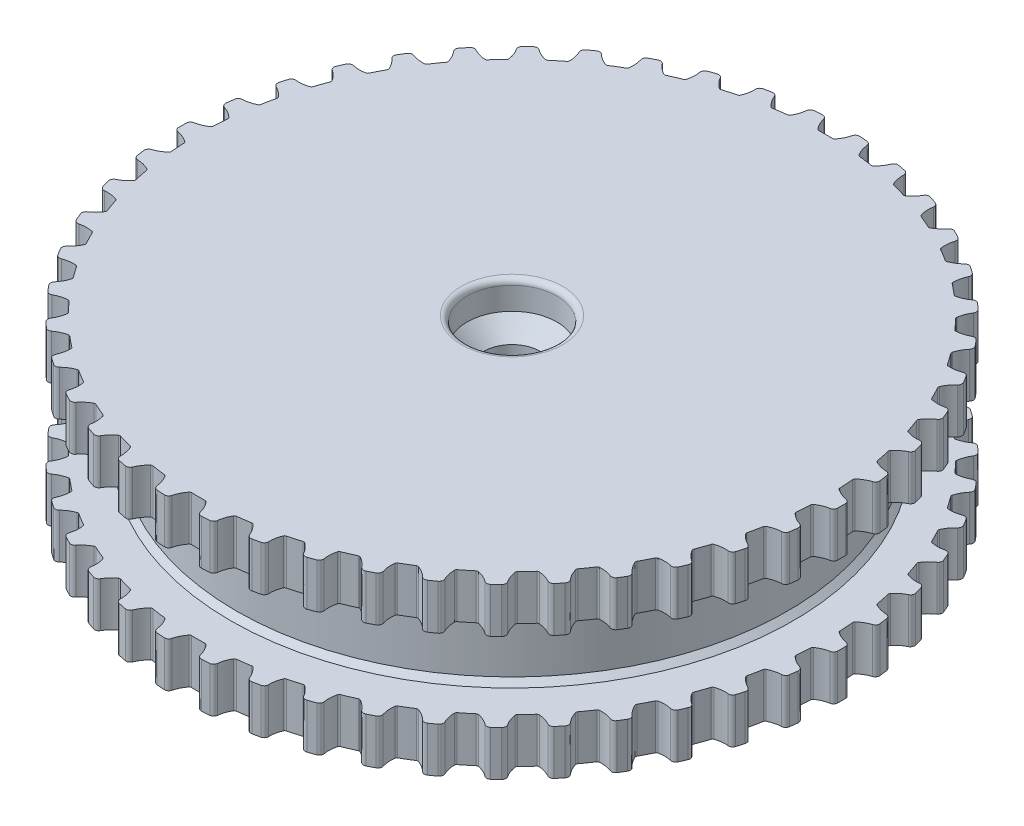
SolidWorks part; units mm, degrees
ref_plane "Front Plane" through (0, 0, 0) normal (0, 0, 1) x (1, 0, 0)
ref_plane "Top Plane" through (0, 0, 0) normal (0, 1, 0) x (1, 0, 0)
ref_plane "Right Plane" through (0, 0, 0) normal (1, 0, 0) x (0, 0, -1)
sketch "Sketch1" plane through (0, 0, 0) normal (0, 1, 0) x (1, 0, 0)
  circle A0 centre (0, 0) radius 62.5
  dimension "D1" = 125
extrude "Boss-Extrude1" add sketch "Sketch1" along normal blind 2
sketch "Sketch2" plane through (0, 2, 0) normal (0, 1, 0) x (1, 0, 0)
  line L0 (0, 0) -> (0, 59.255) construction
  line L2 (2.6, 59.1979) -> (2.6, 58.5113) construction
  line L3 (2.6, 58.5113) -> (-2.6, 58.5113) construction
  line L4 (-2.6, 58.5113) -> (-2.6, 59.1979) construction
  line L5 (0, 0) -> (8.0686, 58.7031) construction
  line L6 (0, 58.569) -> (7.9751, 58.0235) construction
  circle A0 centre (0, 0) radius 59.255 construction
  arc A1 (-54.2415, -22.0951) -> (-53.1706, -24.5605) centre (0, 0) ccw construction
  arc A2 (-2.655, 58.5088) -> (-1.5289, 55.875) centre (2.6, 59.1979) ccw
  circle A4 centre (0, 0) radius 55.739 construction
  arc A6 (1.5289, 55.875) -> (2.655, 58.5088) centre (-2.6, 59.1979) ccw
  arc A7 (1.2087, 55.7259) -> (-1.2087, 55.7259) centre (0, 0) ccw
  arc A8 (-1.5289, 55.875) -> (-1.2087, 55.7259) centre (-1.2173, 56.1258) ccw
  arc A9 (1.2087, 55.7259) -> (1.5289, 55.875) centre (1.2173, 56.1258) ccw
  arc A10 (8.7854, 55.0423) -> (6.3906, 55.3715) centre (0, 0) ccw
  arc A11 (8.7854, 55.0423) -> (9.123, 55.1464) centre (8.8485, 55.4373) ccw
  arc A12 (9.123, 55.1464) -> (10.5972, 57.6023) centre (5.485, 59.0006) ccw
  arc A13 (5.3367, 58.3254) -> (6.0936, 55.5628) centre (10.6366, 58.2925) ccw
  arc A14 (6.0936, 55.5628) -> (6.3906, 55.3715) centre (6.4365, 55.7688) ccw
  arc A15 (16.1985, 53.3334) -> (13.8708, 53.9855) centre (0, 0) ccw
  arc A16 (16.1985, 53.3334) -> (16.5472, 53.3905) centre (16.3148, 53.7161) ccw
  arc A17 (16.5472, 53.3905) -> (18.342, 55.6228) centre (13.4678, 57.7042) ccw
  arc A18 (13.2289, 57.0555) -> (13.6027, 54.2155) centre (18.475, 56.3013) ccw
  arc A19 (13.6027, 54.2155) -> (13.8708, 53.9855) centre (13.9704, 54.373) ccw
  arc A20 (23.3099, 50.6309) -> (21.0927, 51.594) centre (0, 0) ccw
  arc A21 (23.3099, 50.6309) -> (23.663, 50.6401) centre (23.4771, 50.9942) ccw
  arc A22 (23.663, 50.6401) -> (25.7452, 52.6072) centre (21.1998, 55.3329) ccw
  arc A23 (20.8748, 54.7227) -> (20.8583, 51.8583) centre (25.9693, 53.2612) ccw
  arc A24 (20.8583, 51.8583) -> (21.0927, 51.594) centre (21.244, 51.9642) ccw
  arc A25 (29.987, 46.9853) -> (27.9216, 48.2413) centre (0, 0) ccw
  arc A26 (29.987, 46.9853) -> (30.3381, 46.9463) centre (30.2022, 47.3225) ccw
  arc A27 (30.3381, 46.9463) -> (32.6687, 48.6116) centre (28.5368, 51.9308) ccw
  arc A28 (28.1318, 51.3706) -> (27.7254, 48.5351) centre (32.9798, 49.229) ccw
  arc A29 (27.7254, 48.5351) -> (27.9216, 48.2413) centre (28.122, 48.5875) ccw
  arc A30 (36.1055, 42.4645) -> (34.2304, 43.99) centre (0, 0) ccw
  arc A31 (36.1055, 42.4645) -> (36.4481, 42.378) centre (36.3646, 42.7692) ccw
  arc A32 (36.4481, 42.378) -> (38.9837, 43.7104) centre (35.3423, 47.5613) ccw
  arc A33 (34.8647, 47.0615) -> (34.076, 44.3078) centre (39.376, 44.2797) ccw
  arc A34 (34.076, 44.3078) -> (34.2304, 43.99) centre (34.476, 44.3057) ccw
  arc A35 (41.5515, 37.1526) -> (39.9015, 38.9192) centre (0, 0) ccw
  arc A36 (41.5515, 37.1526) -> (41.8791, 37.0203) centre (41.8497, 37.4192) ccw
  arc A37 (41.8791, 37.0203) -> (44.5725, 37.995) centre (41.4894, 42.3059) ccw
  arc A38 (40.9482, 41.8757) -> (39.7919, 39.2551) centre (45.0386, 38.5056) ccw
  arc A39 (39.7919, 39.2551) -> (39.9015, 38.9192) centre (40.1879, 39.1985) ccw
  arc A40 (46.2234, 31.1486) -> (44.8294, 33.1235) centre (0, 0) ccw
  arc A41 (46.2234, 31.1486) -> (46.5299, 30.9729) centre (46.5551, 31.3721) ccw
  arc A42 (46.5299, 30.9729) -> (49.331, 31.5718) centre (46.8636, 36.2624) ccw
  arc A43 (46.2688, 35.9099) -> (44.7665, 33.4711) centre (49.8623, 32.0142) ccw
  arc A44 (44.7665, 33.4711) -> (44.8294, 33.1235) centre (45.1511, 33.3612) ccw
  arc A45 (50.0343, 24.5644) -> (48.9222, 26.7107) centre (0, 0) ccw
  arc A46 (50.0343, 24.5644) -> (50.314, 24.3486) centre (50.3933, 24.7407) ccw
  arc A47 (50.314, 24.3486) -> (53.1706, 24.5605) centre (51.3648, 29.5434) ccw
  arc A48 (50.7276, 29.2752) -> (48.9072, 27.0637) centre (53.7572, 24.9264) ccw
  arc A49 (48.9072, 27.0637) -> (48.9222, 26.7107) centre (49.2732, 26.9024) ccw
  arc A50 (52.9131, 17.5226) -> (52.1036, 19.8003) centre (0, 0) ccw
  arc A51 (52.9131, 17.5226) -> (53.1609, 17.2707) centre (53.2928, 17.6483) ccw
  arc A52 (53.1609, 17.2707) -> (56.0197, 17.0917) centre (54.9092, 22.2741) ccw
  arc A53 (54.2415, 22.0951) -> (52.1368, 20.1521) centre (56.6506, 17.3743) ccw
  arc A54 (52.1368, 20.1521) -> (52.1036, 19.8003) centre (52.4775, 19.9424) ccw
  arc A55 (54.8063, 10.1544) -> (54.3144, 12.5211) centre (0, 0) ccw
  arc A56 (54.8063, 10.1544) -> (55.0174, 9.8711) centre (55.1996, 10.2273) ccw
  arc A57 (55.0174, 9.8711) -> (57.8252, 9.3045) centre (57.4308, 14.5898) ccw
  arc A58 (56.7449, 14.5034) -> (54.3953, 12.8651) centre (58.4888, 9.4986) ccw
  arc A59 (54.3953, 12.8651) -> (54.3144, 12.5211) centre (54.7042, 12.611) ccw
  arc A60 (55.6785, 2.597) -> (55.5135, 5.0087) centre (0, 0) ccw
  arc A61 (55.6785, 2.597) -> (55.8491, 2.2877) centre (56.0781, 2.6157) ccw
  arc A62 (55.8491, 2.2877) -> (58.5536, 1.344) centre (58.8825, 6.6337) ccw
  arc A63 (58.1912, 6.6416) -> (55.6404, 5.3384) centre (59.2374, 1.4459) ccw
  arc A64 (55.6404, 5.3384) -> (55.5135, 5.0087) centre (55.9119, 5.0447) ccw
  arc A65 (55.5135, -5.0087) -> (55.6785, -2.597) centre (0, 0) ccw
  arc A66 (55.5135, -5.0087) -> (55.6404, -5.3384) centre (55.9119, -5.0447) ccw
  arc A67 (55.6404, -5.3384) -> (58.1912, -6.6416) centre (59.2374, -1.4459) ccw
  arc A68 (58.5536, -1.344) -> (55.8491, -2.2877) centre (58.8825, -6.6337) ccw
  arc A69 (55.8491, -2.2877) -> (55.6785, -2.597) centre (56.0781, -2.6157) ccw
  arc A70 (54.3144, -12.5211) -> (54.8063, -10.1544) centre (0, 0) ccw
  arc A71 (54.3144, -12.5211) -> (54.3953, -12.8651) centre (54.7042, -12.611) ccw
  arc A72 (54.3953, -12.8651) -> (56.7449, -14.5034) centre (58.4888, -9.4986) ccw
  arc A73 (57.8252, -9.3045) -> (55.0174, -9.8711) centre (57.4308, -14.5898) ccw
  arc A74 (55.0174, -9.8711) -> (54.8063, -10.1544) centre (55.1996, -10.2273) ccw
  arc A75 (52.1036, -19.8003) -> (52.9131, -17.5226) centre (0, 0) ccw
  arc A76 (52.1036, -19.8003) -> (52.1368, -20.1521) centre (52.4775, -19.9424) ccw
  arc A77 (52.1368, -20.1521) -> (54.2415, -22.0951) centre (56.6506, -17.3743) ccw
  arc A78 (56.0197, -17.0917) -> (53.1609, -17.2707) centre (54.9092, -22.2741) ccw
  arc A79 (53.1609, -17.2707) -> (52.9131, -17.5226) centre (53.2928, -17.6483) ccw
  arc A80 (48.9222, -26.7107) -> (50.0343, -24.5644) centre (0, 0) ccw
  arc A81 (48.9222, -26.7107) -> (48.9072, -27.0637) centre (49.2732, -26.9024) ccw
  arc A82 (48.9072, -27.0637) -> (50.7276, -29.2752) centre (53.7572, -24.9264) ccw
  arc A83 (53.1706, -24.5605) -> (50.314, -24.3486) centre (51.3648, -29.5434) ccw
  arc A84 (50.314, -24.3486) -> (50.0343, -24.5644) centre (50.3933, -24.7407) ccw
  arc A85 (44.8294, -33.1235) -> (46.2234, -31.1486) centre (0, 0) ccw
  arc A86 (44.8294, -33.1235) -> (44.7665, -33.4711) centre (45.1511, -33.3612) ccw
  arc A87 (44.7665, -33.4711) -> (46.2688, -35.9099) centre (49.8623, -32.0142) ccw
  arc A88 (49.331, -31.5718) -> (46.5299, -30.9729) centre (46.8636, -36.2624) ccw
  arc A89 (46.5299, -30.9729) -> (46.2234, -31.1486) centre (46.5551, -31.3721) ccw
  arc A90 (39.9015, -38.9192) -> (41.5515, -37.1526) centre (0, 0) ccw
  arc A91 (39.9015, -38.9192) -> (39.7919, -39.2551) centre (40.1879, -39.1985) ccw
  arc A92 (39.7919, -39.2551) -> (40.9482, -41.8757) centre (45.0386, -38.5056) ccw
  arc A93 (44.5725, -37.995) -> (41.8791, -37.0203) centre (41.4894, -42.3059) ccw
  arc A94 (41.8791, -37.0203) -> (41.5515, -37.1526) centre (41.8497, -37.4192) ccw
  arc A95 (34.2304, -43.99) -> (36.1055, -42.4645) centre (0, 0) ccw
  arc A96 (34.2304, -43.99) -> (34.076, -44.3078) centre (34.476, -44.3057) ccw
  arc A97 (34.076, -44.3078) -> (34.8647, -47.0615) centre (39.376, -44.2797) ccw
  arc A98 (38.9837, -43.7104) -> (36.4481, -42.378) centre (35.3423, -47.5613) ccw
  arc A99 (36.4481, -42.378) -> (36.1055, -42.4645) centre (36.3646, -42.7692) ccw
  arc A100 (27.9216, -48.2413) -> (29.987, -46.9853) centre (0, 0) ccw
  arc A101 (27.9216, -48.2413) -> (27.7254, -48.5351) centre (28.122, -48.5875) ccw
  arc A102 (27.7254, -48.5351) -> (28.1318, -51.3706) centre (32.9798, -49.229) ccw
  arc A103 (32.6687, -48.6116) -> (30.3381, -46.9463) centre (28.5368, -51.9308) ccw
  arc A104 (30.3381, -46.9463) -> (29.987, -46.9853) centre (30.2022, -47.3225) ccw
  arc A105 (21.0927, -51.594) -> (23.3099, -50.6309) centre (0, 0) ccw
  arc A106 (21.0927, -51.594) -> (20.8583, -51.8583) centre (21.244, -51.9642) ccw
  arc A107 (20.8583, -51.8583) -> (20.8748, -54.7227) centre (25.9693, -53.2612) ccw
  arc A108 (25.7452, -52.6072) -> (23.663, -50.6401) centre (21.1998, -55.3329) ccw
  arc A109 (23.663, -50.6401) -> (23.3099, -50.6309) centre (23.4771, -50.9942) ccw
  arc A110 (13.8708, -53.9855) -> (16.1985, -53.3334) centre (0, 0) ccw
  arc A111 (13.8708, -53.9855) -> (13.6027, -54.2155) centre (13.9704, -54.373) ccw
  arc A112 (13.6027, -54.2155) -> (13.2289, -57.0555) centre (18.475, -56.3013) ccw
  arc A113 (18.342, -55.6228) -> (16.5472, -53.3905) centre (13.4678, -57.7042) ccw
  arc A114 (16.5472, -53.3905) -> (16.1985, -53.3334) centre (16.3148, -53.7161) ccw
  arc A115 (6.3906, -55.3715) -> (8.7854, -55.0423) centre (0, 0) ccw
  arc A116 (6.3906, -55.3715) -> (6.0936, -55.5628) centre (6.4365, -55.7688) ccw
  arc A117 (6.0936, -55.5628) -> (5.3367, -58.3254) centre (10.6366, -58.2925) ccw
  arc A118 (10.5972, -57.6023) -> (9.123, -55.1464) centre (5.485, -59.0006) ccw
  arc A119 (9.123, -55.1464) -> (8.7854, -55.0423) centre (8.8485, -55.4373) ccw
  arc A120 (-1.2087, -55.7259) -> (1.2087, -55.7259) centre (0, 0) ccw
  arc A121 (-1.2087, -55.7259) -> (-1.5289, -55.875) centre (-1.2173, -56.1258) ccw
  arc A122 (-1.5289, -55.875) -> (-2.655, -58.5088) centre (2.6, -59.1979) ccw
  arc A123 (2.655, -58.5088) -> (1.5289, -55.875) centre (-2.6, -59.1979) ccw
  arc A124 (1.5289, -55.875) -> (1.2087, -55.7259) centre (1.2173, -56.1258) ccw
  arc A125 (-8.7854, -55.0423) -> (-6.3906, -55.3715) centre (0, 0) ccw
  arc A126 (-8.7854, -55.0423) -> (-9.123, -55.1464) centre (-8.8485, -55.4373) ccw
  arc A127 (-9.123, -55.1464) -> (-10.5972, -57.6023) centre (-5.485, -59.0006) ccw
  arc A128 (-5.3367, -58.3254) -> (-6.0936, -55.5628) centre (-10.6366, -58.2925) ccw
  arc A129 (-6.0936, -55.5628) -> (-6.3906, -55.3715) centre (-6.4365, -55.7688) ccw
  arc A130 (-16.1985, -53.3334) -> (-13.8708, -53.9855) centre (0, 0) ccw
  arc A131 (-16.1985, -53.3334) -> (-16.5472, -53.3905) centre (-16.3148, -53.7161) ccw
  arc A132 (-16.5472, -53.3905) -> (-18.342, -55.6228) centre (-13.4678, -57.7042) ccw
  arc A133 (-13.2289, -57.0555) -> (-13.6027, -54.2155) centre (-18.475, -56.3013) ccw
  arc A134 (-13.6027, -54.2155) -> (-13.8708, -53.9855) centre (-13.9704, -54.373) ccw
  arc A135 (-23.3099, -50.6309) -> (-21.0927, -51.594) centre (0, 0) ccw
  arc A136 (-23.3099, -50.6309) -> (-23.663, -50.6401) centre (-23.4771, -50.9942) ccw
  arc A137 (-23.663, -50.6401) -> (-25.7452, -52.6072) centre (-21.1998, -55.3329) ccw
  arc A138 (-20.8748, -54.7227) -> (-20.8583, -51.8583) centre (-25.9693, -53.2612) ccw
  arc A139 (-20.8583, -51.8583) -> (-21.0927, -51.594) centre (-21.244, -51.9642) ccw
  arc A140 (-29.987, -46.9853) -> (-27.9216, -48.2413) centre (0, 0) ccw
  arc A141 (-29.987, -46.9853) -> (-30.3381, -46.9463) centre (-30.2022, -47.3225) ccw
  arc A142 (-30.3381, -46.9463) -> (-32.6687, -48.6116) centre (-28.5368, -51.9308) ccw
  arc A143 (-28.1318, -51.3706) -> (-27.7254, -48.5351) centre (-32.9798, -49.229) ccw
  arc A144 (-27.7254, -48.5351) -> (-27.9216, -48.2413) centre (-28.122, -48.5875) ccw
  arc A145 (-36.1055, -42.4645) -> (-34.2304, -43.99) centre (0, 0) ccw
  arc A146 (-36.1055, -42.4645) -> (-36.4481, -42.378) centre (-36.3646, -42.7692) ccw
  arc A147 (-36.4481, -42.378) -> (-38.9837, -43.7104) centre (-35.3423, -47.5613) ccw
  arc A148 (-34.8647, -47.0615) -> (-34.076, -44.3078) centre (-39.376, -44.2797) ccw
  arc A149 (-34.076, -44.3078) -> (-34.2304, -43.99) centre (-34.476, -44.3057) ccw
  arc A150 (-41.5515, -37.1526) -> (-39.9015, -38.9192) centre (0, 0) ccw
  arc A151 (-41.5515, -37.1526) -> (-41.8791, -37.0203) centre (-41.8497, -37.4192) ccw
  arc A152 (-41.8791, -37.0203) -> (-44.5725, -37.995) centre (-41.4894, -42.3059) ccw
  arc A153 (-40.9482, -41.8757) -> (-39.7919, -39.2551) centre (-45.0386, -38.5056) ccw
  arc A154 (-39.7919, -39.2551) -> (-39.9015, -38.9192) centre (-40.1879, -39.1985) ccw
  arc A155 (-46.2234, -31.1486) -> (-44.8294, -33.1235) centre (0, 0) ccw
  arc A156 (-46.2234, -31.1486) -> (-46.5299, -30.9729) centre (-46.5551, -31.3721) ccw
  arc A157 (-46.5299, -30.9729) -> (-49.331, -31.5718) centre (-46.8636, -36.2624) ccw
  arc A158 (-46.2688, -35.9099) -> (-44.7665, -33.4711) centre (-49.8623, -32.0142) ccw
  arc A159 (-44.7665, -33.4711) -> (-44.8294, -33.1235) centre (-45.1511, -33.3612) ccw
  arc A160 (-50.0343, -24.5644) -> (-48.9222, -26.7107) centre (0, 0) ccw
  arc A161 (-50.0343, -24.5644) -> (-50.314, -24.3486) centre (-50.3933, -24.7407) ccw
  arc A162 (-50.314, -24.3486) -> (-53.1706, -24.5605) centre (-51.3648, -29.5434) ccw
  arc A163 (-50.7276, -29.2752) -> (-48.9072, -27.0637) centre (-53.7572, -24.9264) ccw
  arc A164 (-48.9072, -27.0637) -> (-48.9222, -26.7107) centre (-49.2732, -26.9024) ccw
  arc A165 (-52.9131, -17.5226) -> (-52.1036, -19.8003) centre (0, 0) ccw
  arc A166 (-52.9131, -17.5226) -> (-53.1609, -17.2707) centre (-53.2928, -17.6483) ccw
  arc A167 (-53.1609, -17.2707) -> (-56.0197, -17.0917) centre (-54.9092, -22.2741) ccw
  arc A168 (-54.2415, -22.0951) -> (-52.1368, -20.1521) centre (-56.6506, -17.3743) ccw
  arc A169 (-52.1368, -20.1521) -> (-52.1036, -19.8003) centre (-52.4775, -19.9424) ccw
  arc A170 (-54.8063, -10.1544) -> (-54.3144, -12.5211) centre (0, 0) ccw
  arc A171 (-54.8063, -10.1544) -> (-55.0174, -9.8711) centre (-55.1996, -10.2273) ccw
  arc A172 (-55.0174, -9.8711) -> (-57.8252, -9.3045) centre (-57.4308, -14.5898) ccw
  arc A173 (-56.7449, -14.5034) -> (-54.3953, -12.8651) centre (-58.4888, -9.4986) ccw
  arc A174 (-54.3953, -12.8651) -> (-54.3144, -12.5211) centre (-54.7042, -12.611) ccw
  arc A176 (7.9751, 58.0235) -> (0, 58.569) centre (0, 0) ccw construction
  arc A177 (-2.655, 58.5088) -> (56.0197, 17.0917) centre (0, 0) ccw construction
  arc A179 (-6.3906, 55.3715) -> (-8.7854, 55.0423) centre (0, 0) ccw
  arc A180 (-6.3906, 55.3715) -> (-6.0936, 55.5628) centre (-6.4365, 55.7688) ccw
  arc A181 (-6.0936, 55.5628) -> (-5.3367, 58.3254) centre (-10.6366, 58.2925) ccw
  arc A182 (-10.5972, 57.6023) -> (-9.123, 55.1464) centre (-5.485, 59.0006) ccw
  arc A183 (-9.123, 55.1464) -> (-8.7854, 55.0423) centre (-8.8485, 55.4373) ccw
  circle A184 centre (0, 0) radius 58.569
  arc A212 (-55.6785, -2.597) -> (-55.5135, -5.0087) centre (0, 0) ccw
  arc A213 (-55.6785, -2.597) -> (-55.8491, -2.2877) centre (-56.0781, -2.6157) ccw
  arc A214 (-55.8491, -2.2877) -> (-58.5536, -1.344) centre (-58.8825, -6.6337) ccw
  arc A215 (-58.1912, -6.6416) -> (-55.6404, -5.3384) centre (-59.2374, -1.4459) ccw
  arc A216 (-55.6404, -5.3384) -> (-55.5135, -5.0087) centre (-55.9119, -5.0447) ccw
  arc A217 (-55.5135, 5.0087) -> (-55.6785, 2.597) centre (0, 0) ccw
  arc A218 (-55.5135, 5.0087) -> (-55.6404, 5.3384) centre (-55.9119, 5.0447) ccw
  arc A219 (-55.6404, 5.3384) -> (-58.1912, 6.6416) centre (-59.2374, 1.4459) ccw
  arc A220 (-58.5536, 1.344) -> (-55.8491, 2.2877) centre (-58.8825, 6.6337) ccw
  arc A221 (-55.8491, 2.2877) -> (-55.6785, 2.597) centre (-56.0781, 2.6157) ccw
  arc A222 (-54.3144, 12.5211) -> (-54.8063, 10.1544) centre (0, 0) ccw
  arc A223 (-54.3144, 12.5211) -> (-54.3953, 12.8651) centre (-54.7042, 12.611) ccw
  arc A224 (-54.3953, 12.8651) -> (-56.7449, 14.5034) centre (-58.4888, 9.4986) ccw
  arc A225 (-57.8252, 9.3045) -> (-55.0174, 9.8711) centre (-57.4308, 14.5898) ccw
  arc A226 (-55.0174, 9.8711) -> (-54.8063, 10.1544) centre (-55.1996, 10.2273) ccw
  arc A227 (-52.1036, 19.8003) -> (-52.9131, 17.5226) centre (0, 0) ccw
  arc A228 (-52.1036, 19.8003) -> (-52.1368, 20.1521) centre (-52.4775, 19.9424) ccw
  arc A229 (-52.1368, 20.1521) -> (-54.2415, 22.0951) centre (-56.6506, 17.3743) ccw
  arc A230 (-56.0197, 17.0917) -> (-53.1609, 17.2707) centre (-54.9092, 22.2741) ccw
  arc A231 (-53.1609, 17.2707) -> (-52.9131, 17.5226) centre (-53.2928, 17.6483) ccw
  arc A232 (-48.9222, 26.7107) -> (-50.0343, 24.5644) centre (0, 0) ccw
  arc A233 (-48.9222, 26.7107) -> (-48.9072, 27.0637) centre (-49.2732, 26.9024) ccw
  arc A234 (-48.9072, 27.0637) -> (-50.7276, 29.2752) centre (-53.7572, 24.9264) ccw
  arc A235 (-53.1706, 24.5605) -> (-50.314, 24.3486) centre (-51.3648, 29.5434) ccw
  arc A236 (-50.314, 24.3486) -> (-50.0343, 24.5644) centre (-50.3933, 24.7407) ccw
  arc A237 (-44.8294, 33.1235) -> (-46.2234, 31.1486) centre (0, 0) ccw
  arc A238 (-44.8294, 33.1235) -> (-44.7665, 33.4711) centre (-45.1511, 33.3612) ccw
  arc A239 (-44.7665, 33.4711) -> (-46.2688, 35.9099) centre (-49.8623, 32.0142) ccw
  arc A240 (-49.331, 31.5718) -> (-46.5299, 30.9729) centre (-46.8636, 36.2624) ccw
  arc A241 (-46.5299, 30.9729) -> (-46.2234, 31.1486) centre (-46.5551, 31.3721) ccw
  arc A242 (-39.9015, 38.9192) -> (-41.5515, 37.1526) centre (0, 0) ccw
  arc A243 (-39.9015, 38.9192) -> (-39.7919, 39.2551) centre (-40.1879, 39.1985) ccw
  arc A244 (-39.7919, 39.2551) -> (-40.9482, 41.8757) centre (-45.0386, 38.5056) ccw
  arc A245 (-44.5725, 37.995) -> (-41.8791, 37.0203) centre (-41.4894, 42.3059) ccw
  arc A246 (-41.8791, 37.0203) -> (-41.5515, 37.1526) centre (-41.8497, 37.4192) ccw
  arc A247 (-34.2304, 43.99) -> (-36.1055, 42.4645) centre (0, 0) ccw
  arc A248 (-34.2304, 43.99) -> (-34.076, 44.3078) centre (-34.476, 44.3057) ccw
  arc A249 (-34.076, 44.3078) -> (-34.8647, 47.0615) centre (-39.376, 44.2797) ccw
  arc A250 (-38.9837, 43.7104) -> (-36.4481, 42.378) centre (-35.3423, 47.5613) ccw
  arc A251 (-36.4481, 42.378) -> (-36.1055, 42.4645) centre (-36.3646, 42.7692) ccw
  arc A252 (-27.9216, 48.2413) -> (-29.987, 46.9853) centre (0, 0) ccw
  arc A253 (-27.9216, 48.2413) -> (-27.7254, 48.5351) centre (-28.122, 48.5875) ccw
  arc A254 (-27.7254, 48.5351) -> (-28.1318, 51.3706) centre (-32.9798, 49.229) ccw
  arc A255 (-32.6687, 48.6116) -> (-30.3381, 46.9463) centre (-28.5368, 51.9308) ccw
  arc A256 (-30.3381, 46.9463) -> (-29.987, 46.9853) centre (-30.2022, 47.3225) ccw
  arc A257 (-21.0927, 51.594) -> (-23.3099, 50.6309) centre (0, 0) ccw
  arc A258 (-21.0927, 51.594) -> (-20.8583, 51.8583) centre (-21.244, 51.9642) ccw
  arc A259 (-20.8583, 51.8583) -> (-20.8748, 54.7227) centre (-25.9693, 53.2612) ccw
  arc A260 (-25.7452, 52.6072) -> (-23.663, 50.6401) centre (-21.1998, 55.3329) ccw
  arc A261 (-23.663, 50.6401) -> (-23.3099, 50.6309) centre (-23.4771, 50.9942) ccw
  arc A262 (-13.8708, 53.9855) -> (-16.1985, 53.3334) centre (0, 0) ccw
  arc A263 (-13.8708, 53.9855) -> (-13.6027, 54.2155) centre (-13.9704, 54.373) ccw
  arc A264 (-13.6027, 54.2155) -> (-13.2289, 57.0555) centre (-18.475, 56.3013) ccw
  arc A265 (-18.342, 55.6228) -> (-16.5472, 53.3905) centre (-13.4678, 57.7042) ccw
  arc A266 (-16.5472, 53.3905) -> (-16.1985, 53.3334) centre (-16.3148, 53.7161) ccw
  arc A277 (-50.7276, -29.2752) -> (-56.0197, -17.0917) centre (0, 0) ccw construction
  arc A278 (50.7276, 29.2752) -> (0, 58.569) centre (0, 0) ccw construction
  arc A279 (54.2415, 22.0951) -> (53.1706, 24.5605) centre (0, 0) ccw construction
  point P5 (0, 29.6275)
  point P15 (0, 55.739)
  point P17 (7.5898, 55.2199)
  point P353 (0, 0)
  dimension "D1" = 5.2
  dimension "D2" = 0.686
  dimension "D3" = 10.6
  dimension "D4" = 2.83
  dimension "D5" = 0.8
  dimension "D7" = 8
  dimension "D6" = 46
extrude "Boss-Extrude2" add sketch "Sketch2" along normal blind 30
fillet "Fillet2" radius 0.75 92 edges at (-2.655, 17, -58.5088) (-5.3367, 17, -58.3254) (5.3367, 17, -58.3254) (2.655, 17, -58.5088) (20.8748, 17, -54.7227) (18.342, 17, -55.6228) (13.2289, 17, -57.0555) (10.5972, 17, -57.6023) (25.7452, 17, -52.6072) (28.1318, 17, -51.3706) (32.6687, 17, -48.6116) (34.8647, 17, -47.0615) (38.9837, 17, -43.7104) (40.9482, 17, -41.8757) (44.5725, 17, -37.995) (46.2688, 17, -35.9099) (49.331, 17, -31.5718) (50.7276, 17, -29.2752) (53.1706, 17, -24.5605) (54.2415, 17, -22.0951) (56.0197, 17, -17.0917) (56.7449, 17, -14.5034) (57.8252, 17, -9.3045) (58.1912, 17, -6.6416) (58.5536, 17, -1.344) (58.5536, 17, 1.344) (58.1912, 17, 6.6416) (57.8252, 17, 9.3045) (56.7449, 17, 14.5034) (56.0197, 17, 17.0917) (53.1706, 17, 24.5605) (54.2415, 17, 22.0951) (50.7276, 17, 29.2752) (49.331, 17, 31.5718) (46.2688, 17, 35.9099) (44.5725, 17, 37.995) (38.9837, 17, 43.7104) (40.9482, 17, 41.8757) (34.8647, 17, 47.0615) (32.6687, 17, 48.6116) (28.1318, 17, 51.3706) (25.7452, 17, 52.6072) (20.8748, 17, 54.7227) (18.342, 17, 55.6228) (13.2289, 17, 57.0555) (10.5972, 17, 57.6023) (5.3367, 17, 58.3254) (2.655, 17, 58.5088) (-2.655, 17, 58.5088) (-5.3367, 17, 58.3254) (-13.2289, 17, 57.0555) (-10.5972, 17, 57.6023) (-18.342, 17, 55.6228) (-20.8748, 17, 54.7227) (-25.7452, 17, 52.6072) (-28.1318, 17, 51.3706) (-32.6687, 17, 48.6116) (-34.8647, 17, 47.0615) (-38.9837, 17, 43.7104) (-40.9482, 17, 41.8757) (-44.5725, 17, 37.995) (-46.2688, 17, 35.9099) (-49.331, 17, 31.5718) (-50.7276, 17, 29.2752) (-53.1706, 17, 24.5605) (-54.2415, 17, 22.0951) (-56.0197, 17, 17.0917) (-56.7449, 17, 14.5034) (-57.8252, 17, 9.3045) (-58.1912, 17, 6.6416) (-58.5536, 17, 1.344) (-58.5536, 17, -1.344) (-58.1912, 17, -6.6416) (-57.8252, 17, -9.3045) (-56.7449, 17, -14.5034) (-56.0197, 17, -17.0917) (-54.2415, 17, -22.0951) (-53.1706, 17, -24.5605) (-50.7276, 17, -29.2752) (-46.2688, 17, -35.9099) (-44.5725, 17, -37.995) (-49.331, 17, -31.5718) (-40.9482, 17, -41.8757) (-38.9837, 17, -43.7104) (-34.8647, 17, -47.0615) (-32.6687, 17, -48.6116) (-28.1318, 17, -51.3706) (-25.7452, 17, -52.6072) (-20.8748, 17, -54.7227) (-18.342, 17, -55.6228) (-13.2289, 17, -57.0555) (-10.5972, 17, -57.6023)
sketch "Sketch3" plane through (0, 32, 0) normal (0, 1, 0) x (1, 0, 0)
  circle A0 centre (0, 0) radius 62.5
  circle A1 centre (0, 0) radius 62.5 construction
extrude "Boss-Extrude3" add sketch "Sketch3" along normal blind 2
sketch "Sketch4" plane through (0, 0, 0) normal (0, -1, 0) x (1, 0, 0)
  circle A0 centre (0, 0) radius 5
  dimension "D1" = 10
extrude "Cut-Extrude1" cut sketch "Sketch4" against normal through all
sketch "Sketch5" plane through (0, 34, 0) normal (0, 1, 0) x (1, 0, 0)
  circle A0 centre (0, 0) radius 8
  dimension "D1" = 16
extrude "Cut-Extrude2" cut sketch "Sketch5" against normal blind 10
sketch "Sketch6" plane through (0, 0, 0) normal (0, -1, 0) x (1, 0, 0)
  circle A0 centre (0, 0) radius 8
  dimension "D1" = 16
extrude "Cut-Extrude3" cut sketch "Sketch6" against normal blind 10
fillet "Fillet3" radius 0.75 2 edges at (0, 34, 8) (0, 0, -8)
sketch "Sketch7" plane through (0, 34, 0) normal (0, 1, 0) x (1, 0, 0)
  circle A0 centre (0, 0) radius 62.5
  circle A1 centre (0, 0) radius 62.5 construction
extrude "Cut-Extrude4" cut sketch "Sketch7" against normal up to surface (2 mm away) up to face at (0, 32, 0)
sketch "Sketch9" plane through (0, 0, 0) normal (0, -1, 0) x (1, 0, 0)
  circle A0 centre (0, 0) radius 62.5
  circle A1 centre (0, 0) radius 62.5 construction
extrude "Cut-Extrude5" cut sketch "Sketch9" against normal up to surface (2 mm away) up to face at (0, 2, 62.5)
chamfer "Chamfer1" distance 3 angle 45 2 edges at (0, 10, -8) (0, 24, 8)
sketch "Sketch10" plane through (0, 0, 0) normal (1, 0, 0) x (0, 0, -1)
  line L0 (0, 2) -> (0, 32) construction
  line L1 (-58.57, 24) -> (-48.97, 24)
  line L2 (-58.57, 24) -> (-58.57, 10)
  line L3 (-58.57, 10) -> (-48.97, 10)
  line L4 (-48.97, 24) -> (-48.97, 10)
  line L5 (0.6875, 32) -> (-0.6875, 32) construction
  line L6 (-58.57, 17) -> (0, 17) construction
  line L7 (-0.6875, 2) -> (0.6875, 2) construction
  dimension "D1" = 14
  dimension "D2" = 9.6
  dimension "D3" = 58.57
revolve "Cut-Revolve1" cut sketch "Sketch10" angle 360 about L0
chamfer "Chamfer2" distance 1 angle 45 2 edges at (0, 10, -48.97) (0, 24, -48.97)
fillet "Fillet4" radius 1 2 edges at (0, 32, 8) (0, 2, 8)
